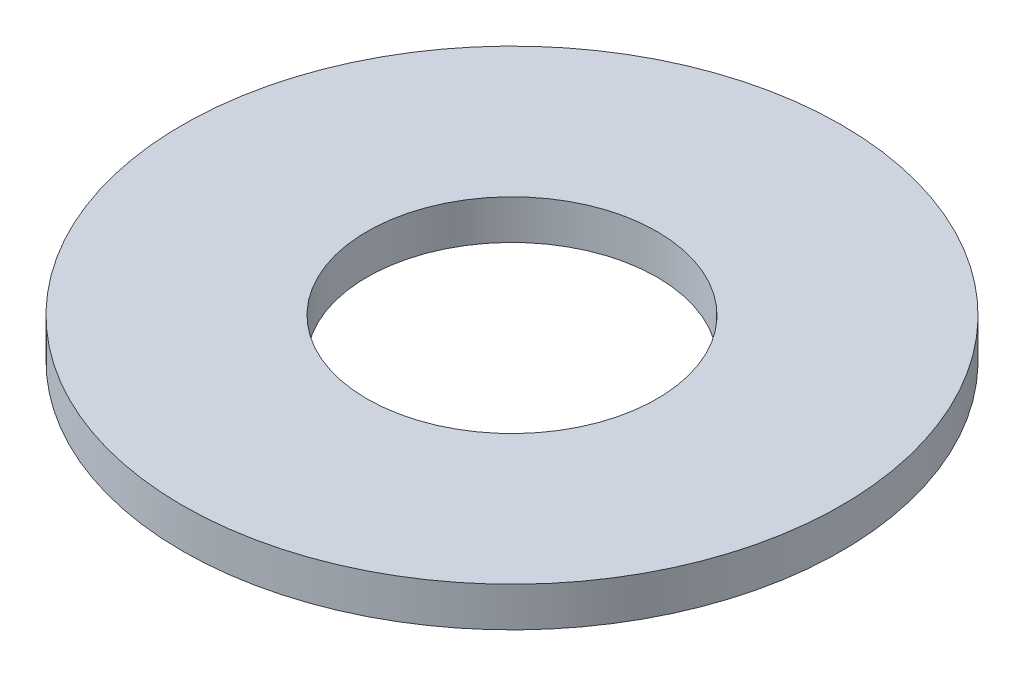
SolidWorks part; units mm, degrees
material "AISI 1020"
ref_plane "Front" through (0, 0, 0) normal (0, 0, 1) x (1, 0, 0)
ref_plane "Top" through (0, 0, 0) normal (0, 1, 0) x (1, 0, 0)
ref_plane "Right" through (0, 0, 0) normal (1, 0, 0) x (0, 0, -1)
ref_axis "X" through (-80.9, 0, 0) along (1, 0, 0)
ref_axis "Y" through (0, -50, 0) along (0, 1, 0)
ref_axis "Z" through (0, 0, -80.9) along (0, 0, 1)
sketch "Sketch1" plane through (0, 0, 0) normal (0, 1, 0) x (1, 0, 0)
  circle A0 centre (0, 0) radius 1.1
  circle A2 centre (0, 0) radius 2.5
  dimension "D1" = 2.2
  dimension "D2" = 5
extrude "Boss-Extrude1" add sketch "Sketch1" along normal mid plane 0.3
